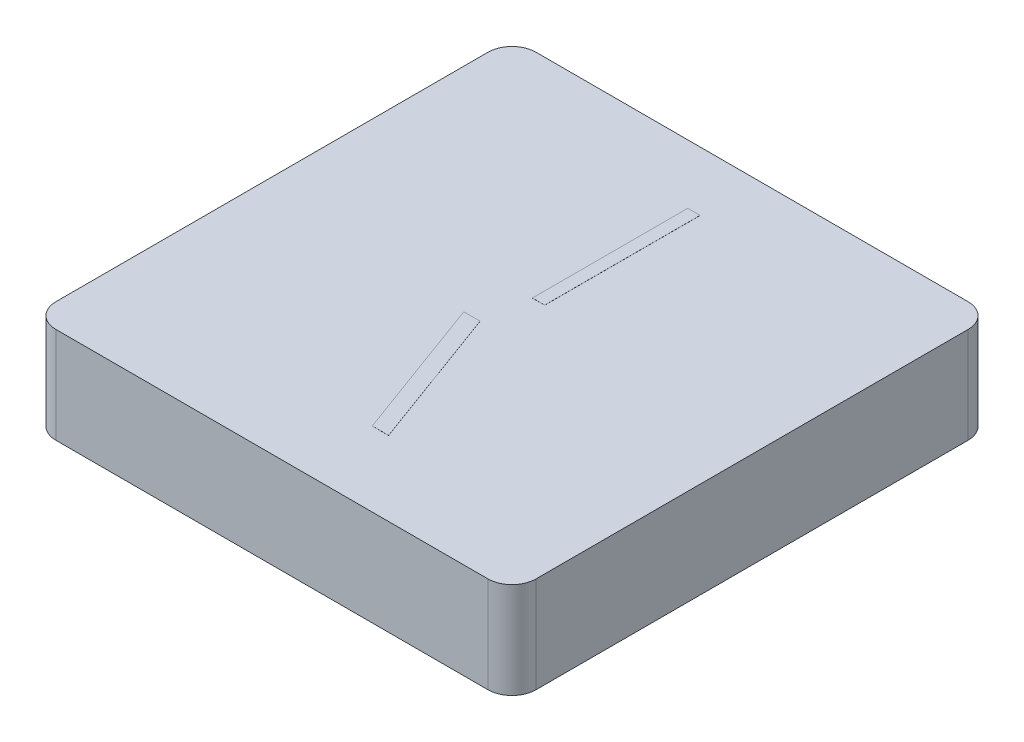
SolidWorks part; units mm, degrees
ref_plane "Front Plane" through (0, 0, 0) normal (0, 0, 1) x (1, 0, 0)
ref_plane "Top Plane" through (0, 0, 0) normal (0, 1, 0) x (1, 0, 0)
ref_plane "Right Plane" through (0, 0, 0) normal (1, 0, 0) x (0, 0, -1)
sketch "Sketch1" plane through (0, 0, 0) normal (0, 1, 0) x (1, 0, 0)
  line L0 (0, 0) -> (12.7, 0)
  line L1 (12.7, 0) -> (12.7, 12.7)
  line L2 (12.7, 12.7) -> (0, 12.7)
  line L3 (0, 12.7) -> (0, 0)
  dimension "D1" = 12.7
  dimension "D2" = 12.7
extrude "Boss-Extrude1" add sketch "Sketch1" along normal blind 2.54
fillet "Fillet1" radius 0.635 4 edges at (0, 1.27, -12.7) (12.7, 1.27, -12.7) (12.7, 1.27, 0) (0, 1.27, 0)
shell "Shell1" thickness 0.635 removed face at (6.35, 0, -6.35)
sketch "Sketch2" plane through (0, 1.905, 0) normal (0, -1, 0) x (-1, 0, 0)
  line L0 (-0.635, 6.35) -> (-12.065, 6.35) construction
  line L1 (-0.635, 12.065) -> (-0.635, 0.635) construction
  line L2 (-12.065, 0.635) -> (-12.065, 12.065) construction
  line L3 (-6.35, 0.635) -> (-6.35, 12.065) construction
  line L4 (-0.635, 0.635) -> (-12.065, 0.635) construction
  line L5 (-12.065, 12.065) -> (-0.635, 12.065) construction
  circle A0 centre (-6.35, 6.35) radius 2.54
  dimension "D1" = 5.08
extrude "Boss-Extrude2" add sketch "Sketch2" along normal up to surface (1.905 mm away) up to face at (6.35, 0, -6.35)
sketch "Sketch4" plane through (0, 2.54, 0) normal (0, 1, 0) x (1, 0, 0)
  line L0 (0, 12.065) -> (0, 0.635) construction
  line L1 (12.065, 12.7) -> (0.635, 12.7) construction
  line L2 (0.635, 0) -> (12.065, 0) construction
  text T0 "<b>\\</b>"
  text T1 "<b>|</b>"
  dimension "D1" = 5.08
  dimension "D2" = 5.1435
  dimension "D3" = 4.826
  dimension "D4" = 2.54
extrude "Boss-Extrude4" add sketch "Sketch4" along normal blind 0.0025
